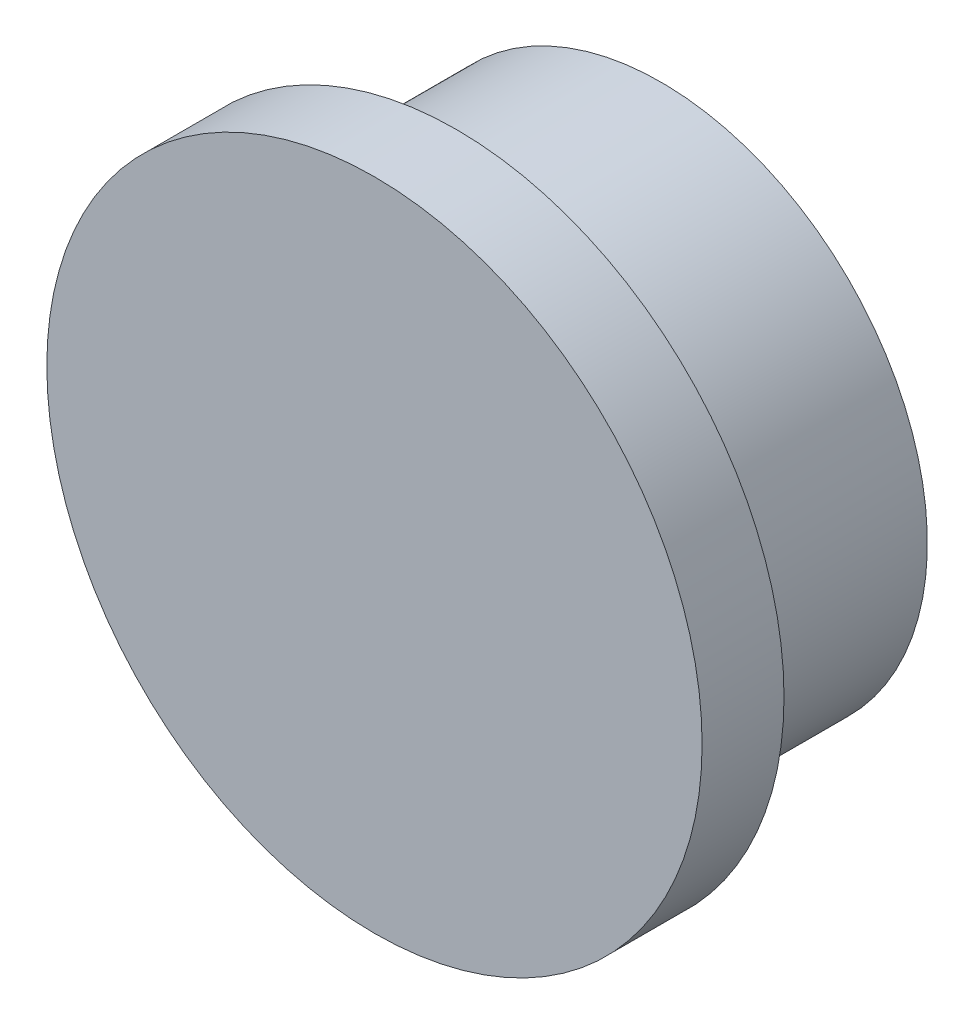
SolidWorks part; units mm, degrees
ref_plane "Front Plane" through (0, 0, 0) normal (0, 0, 1) x (1, 0, 0)
ref_plane "Top Plane" through (0, 0, 0) normal (0, 1, 0) x (1, 0, 0)
ref_plane "Right Plane" through (0, 0, 0) normal (1, 0, 0) x (0, 0, -1)
sketch "Sketch1" plane through (0, 0, 0) normal (0, 0, 1) x (1, 0, 0)
  circle A0 centre (-127.9925, 40.1033) radius 12
extrude "Boss-Extrude1" add sketch "Sketch1" along normal blind 3
sketch "Sketch2" plane through (0, 0, 0) normal (0, 0, -1) x (-1, 0, 0)
  circle A1 centre (127.9925, 40.1033) radius 9.75
extrude "Boss-Extrude2" add sketch "Sketch2" along normal blind 7.5
sketch "Sketch3" plane through (0, 0, -7.5) normal (0, 0, -1) x (-1, 0, 0)
  circle A1 centre (127.9925, 40.1033) radius 2.35
extrude "Cut-Extrude1" cut sketch "Sketch3" against normal blind 5
